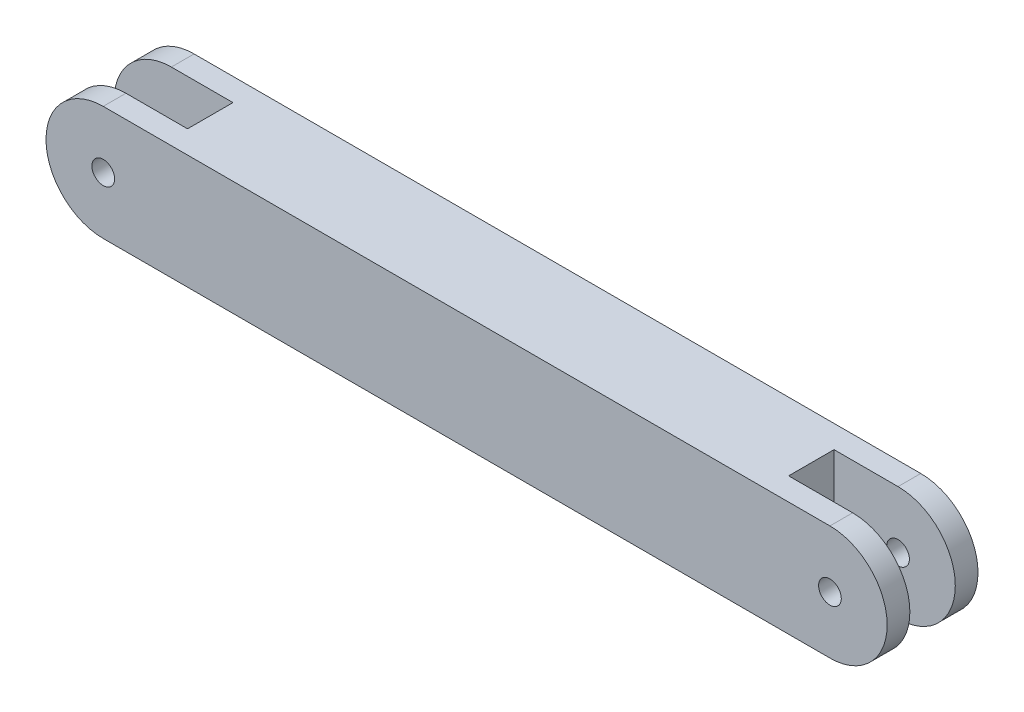
SolidWorks part; units mm, degrees
ref_plane "Front" through (0, 0, 0) normal (0, 0, 1) x (1, 0, 0)
ref_plane "Top" through (0, 0, 0) normal (0, 1, 0) x (1, 0, 0)
ref_plane "Right" through (0, 0, 0) normal (1, 0, 0) x (0, 0, -1)
sketch "Sketch1" plane through (0, 0, 0) normal (0, 0, 1) x (1, 0, 0)
  line L0 (-47.2174, -8.0781) -> (155.9826, -8.0781) construction
  line L1 (-47.2174, 7.9239) -> (155.9826, 7.9239)
  line L2 (-47.2174, -24.0801) -> (155.9826, -24.0801)
  arc A0 (-47.2174, 7.9239) -> (-47.2174, -24.0801) centre (-47.2174, -8.0781) ccw
  arc A1 (155.9826, -24.0801) -> (155.9826, 7.9239) centre (155.9826, -8.0781) ccw
  circle A2 centre (-47.2174, -8.0781) radius 3.175
  circle A3 centre (155.9826, -8.0781) radius 3.175
  point P2 (54.3826, -8.0781)
  dimension "D1" = 16.002
  dimension "D3" = 6.35
  dimension "D4" = 6.35
  dimension "D2" = 203.2
extrude "Boss-Extrude1" add sketch "Sketch1" along normal blind 6.35
sketch "Sketch2" plane through (0, 0, 6.35) normal (0, 0, 1) x (1, 0, 0)
  line L2 (-29.9926, -24.0801) -> (-29.9926, 7.9239)
  line L4 (155.9826, 7.9239) -> (-47.2174, 7.9239) construction
  line L7 (-47.2174, -24.0801) -> (155.9826, -24.0801) construction
  line L9 (138.0826, -24.0801) -> (138.0826, 7.9239)
  line L10 (-29.9926, 7.9239) -> (138.0826, 7.9239)
  line L11 (-29.9926, -24.0801) -> (138.0826, -24.0801)
  point P0 (-29.9926, -24.0801)
  point P13 (-29.9926, -8.0781)
  point P16 (16.9972, 0.4239)
  point P24 (138.0826, -8.0781)
extrude "Boss-Extrude2" add sketch "Sketch2" along normal blind 12.7
sketch "Sketch5" plane through (0, 0, 19.05) normal (0, 0, 1) x (1, 0, 0)
  line L0 (-47.2174, -8.0781) -> (155.9826, -8.0781) construction
  line L1 (-47.2174, 7.9239) -> (155.9826, 7.9239)
  line L2 (-47.2174, -24.0801) -> (155.9826, -24.0801)
  arc A0 (-47.2174, 7.9239) -> (-47.2174, -24.0801) centre (-47.2174, -8.0781) ccw
  arc A1 (155.9826, -24.0801) -> (155.9826, 7.9239) centre (155.9826, -8.0781) ccw
  circle A2 centre (-47.2174, -8.0781) radius 3.175
  circle A3 centre (155.9826, -8.0781) radius 3.175
  point P4 (54.3826, -8.0781)
  dimension "D1" = 16.002
  dimension "D2" = 6.35
  dimension "D3" = 6.35
extrude "Boss-Extrude3" add sketch "Sketch5" along normal blind 6.35
